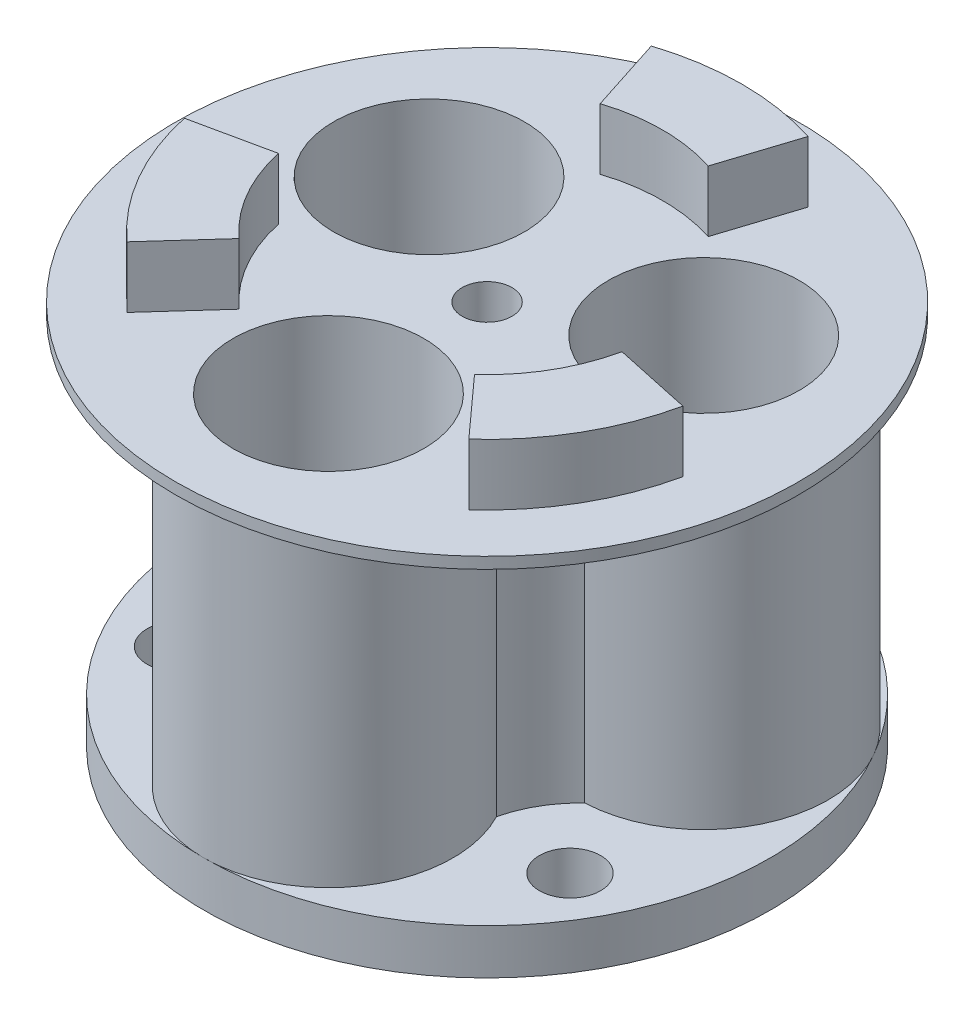
SolidWorks part; units mm, degrees
ref_plane "Front Plane" through (0, 0, 0) normal (0, 0, 1) x (1, 0, 0)
ref_plane "Top Plane" through (0, 0, 0) normal (0, 1, 0) x (1, 0, 0)
ref_plane "Right Plane" through (0, 0, 0) normal (1, 0, 0) x (0, 0, -1)
sketch "Sketch1" plane through (0, 0, 0) normal (0, 1, 0) x (1, 0, 0)
  line L0 (0, -55) -> (0, 55) construction
  circle A0 centre (0, 0) radius 27.5
  circle A1 centre (0, 0) radius 2.2
  circle A2 centre (0, -14) radius 8.425
  circle A3 centre (-12.1244, 7) radius 8.425
  circle A4 centre (12.1244, 7) radius 8.425
  point P14 (0, 0)
  dimension "D1" = 55
  dimension "D2" = 4.4
  dimension "D3" = 16.85
  dimension "D4" = 14
  dimension "D5" = 3
extrude "Boss-Extrude1" add sketch "Sketch1" along normal blind 34
ref_plane "Plane1" through (0, 4, 0) normal (0, 1, 0) x (1, 0, 0)
sketch "Sketch4" plane through (0, 34, 0) normal (0, 1, 0) x (1, 0, 0)
  line L0 (0, 0) -> (23.6709, -13.6664) construction
  line L1 (-22.0001, -4.7164) -> (-15.1556, -3.2491)
  line L2 (0, -55) -> (0, 55) construction
  line L3 (15.0846, -16.6945) -> (10.3916, -11.5006)
  line L4 (22.0001, -4.7164) -> (15.1556, -3.2491)
  line L5 (-15.0846, -16.6945) -> (-10.3916, -11.5006)
  line L6 (6.9155, 21.4109) -> (4.764, 14.7497)
  line L7 (-6.9155, 21.4109) -> (-4.764, 14.7497)
  circle A0 centre (0, 0) radius 22.5
  circle A2 centre (0, 0) radius 15.5
  point P23 (-1.3727, 0.446)
  point P24 (0, 0)
  dimension "D1" = 45
  dimension "D2" = 7
  dimension "D3" = 60
  dimension "D4" = 35.8
  dimension "D5" = 3
extrude "Boss-Extrude2" add sketch "Sketch4" along normal blind 5.4 contours A2 A0 | A2 A0 | L0 A2 L3 A0 | A2 L0 A0 L4 region at (17.8598, 34, 6.8736) region at (14.8826, 34, 12.0302) region at (-16.3712, 34, 9.4519) region at (0, 34, -18.9039)
sketch "Sketch5" plane through (0, 4, 0) normal (0, 1, 0) x (1, 0, 0)
  circle A0 centre (-12.1244, 7) radius 11
  circle A1 centre (0, 0) radius 22.5 construction
  circle A2 centre (0, 22.5) radius 10
  circle A3 centre (0, 0) radius 40.9893
  circle A4 centre (12.1244, 7) radius 11
  circle A5 centre (19.4856, -11.25) radius 10
  circle A6 centre (0, -14) radius 11
  circle A7 centre (-19.4856, -11.25) radius 10
  point P20 (0, 0)
  dimension "D1" = 22
  dimension "D2" = 20
  dimension "D3" = 45
  dimension "D4" = 3
extrude "Cut-Extrude1" cut sketch "Sketch5" along normal blind 29 contours A3 A7 A0 A2 A4 A5 A6 | A6 A5 A4 | A4 A2 A0 | A6 A7 A0 region at (0, 4, -22.8169) region at (-19.76, 4, 11.4085) region at (19.76, 4, 11.4085) region at (-39.8299, 4, 0)
sketch "Sketch6" plane through (0, 0, 0) normal (0, -1, 0) x (1, 0, 0)
  circle A0 centre (0, 0) radius 20 construction
  circle A1 centre (0, -20) radius 2.7
  circle A2 centre (-17.3205, 10) radius 2.7
  circle A3 centre (17.3205, 10) radius 2.7
  point P11 (0, 0)
  dimension "D1" = 40
  dimension "D2" = 5.4
  dimension "D3" = 3
extrude "Cut-Extrude2" cut sketch "Sketch6" against normal blind 5
sketch "Sketch7" plane through (0, 0, 0) normal (0, -1, 0) x (1, 0, 0)
  circle A0 centre (0, 0) radius 25
  circle A2 centre (0, 0) radius 33.7565
  circle M6 centre (0, 0) radius 27.5
  dimension "D1" = 50
extrude "Cut-Extrude6" cut sketch "Sketch7" against normal blind 4 contours A0 M6 | A2 M6 region at (-32.8017, 0, 0) region at (-26.7222, 0, 0)
